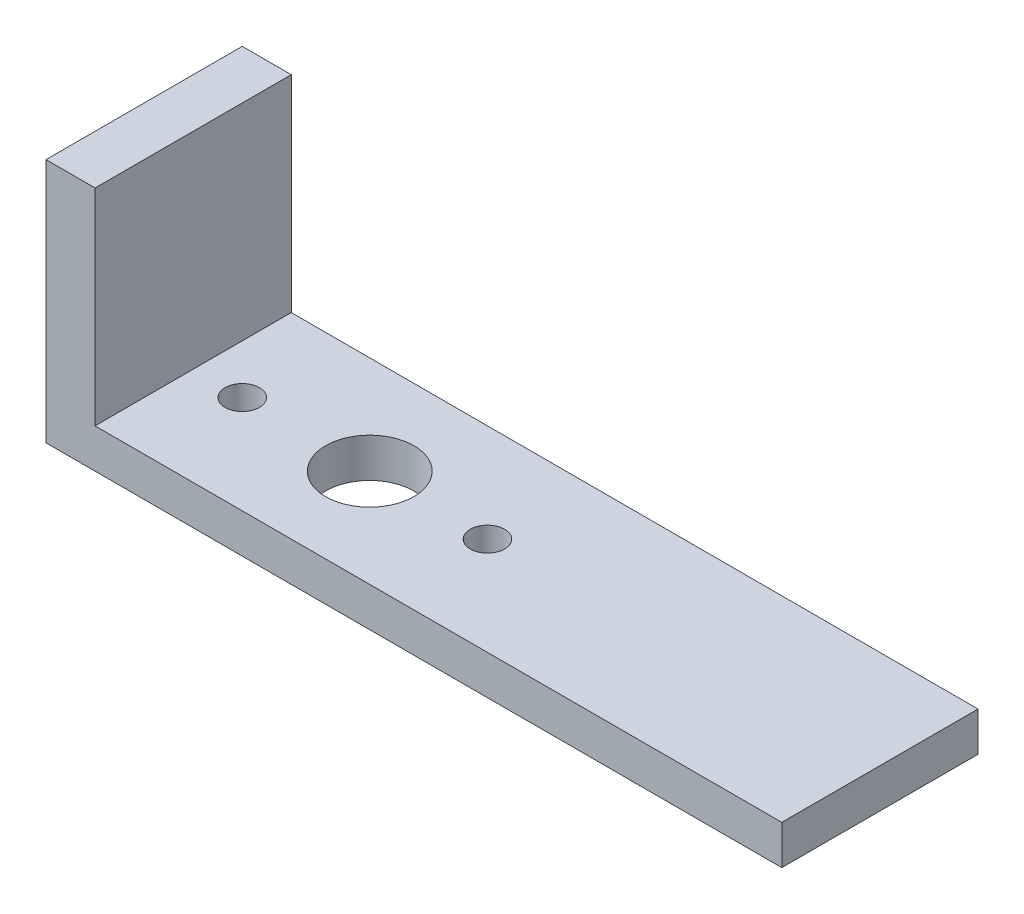
SolidWorks part; units mm, degrees
ref_plane "前视基准面" through (0, 0, 0) normal (0, 0, 1) x (1, 0, 0)
ref_plane "上视基准面" through (0, 0, 0) normal (0, 1, 0) x (1, 0, 0)
ref_plane "右视基准面" through (0, 0, 0) normal (1, 0, 0) x (0, 0, -1)
sketch "草图1" plane through (0, 0, 0) normal (0, 1, 0) x (1, 0, 0)
  line L0 (0, 0) -> (0, 20)
  line L1 (0, 20) -> (75, 20)
  line L2 (75, 20) -> (75, 0)
  line L3 (75, 0) -> (0, 0)
  line L4 (5, 20) -> (5, 0)
  circle A0 centre (10, 10) radius 1.75
  circle A1 centre (35, 10) radius 1.75
  circle A2 centre (23, 10) radius 4.5
  dimension "D5" = 3.5
  dimension "D6" = 3.5
  dimension "D9" = 9
  dimension "D1" = 20
  dimension "D2" = 75
  dimension "D3" = 10
  dimension "D4" = 25
  dimension "D7" = 10
  dimension "D8" = 5
  dimension "D10" = 13
extrude "凸台-拉伸1" add sketch "草图1" along normal blind 4 contours L1 L4 L3 L2 A1 A0 region at (41.0768, 0, -10)
extrude "凸台-拉伸2" add sketch "草图1<3>" along normal blind 25 contours L4 L1 L0 L3 region at (2.5, 0, -10)
sketch "草图1<3>" plane through (0, 0, 0) normal (0, 1, 0) x (1, 0, 0) same geometry as "草图1"
